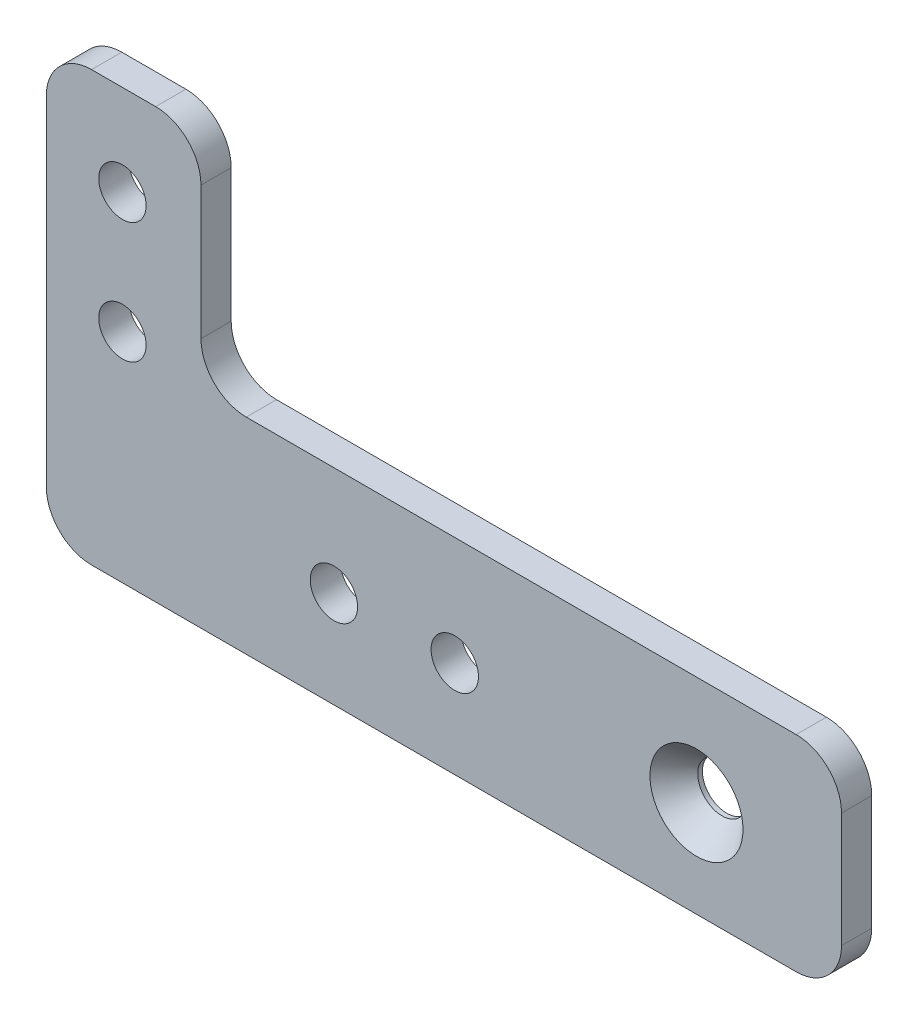
SolidWorks part; units mm, degrees
material "6061-T6 (SS)"
ref_plane "Front Plane" through (0, 0, 0) normal (0, 0, 1) x (1, 0, 0)
ref_plane "Top Plane" through (0, 0, 0) normal (0, 1, 0) x (1, 0, 0)
ref_plane "Right Plane" through (0, 0, 0) normal (1, 0, 0) x (0, 0, -1)
sketch "Sketch1" plane through (0, 0, 0) normal (0, 0, 1) x (1, 0, 0)
  line L0 (-21.59, 23.8125) -> (-37.846, 23.8125) construction
  line L1 (-45.72, -23.8125) -> (45.72, -23.8125)
  line L2 (-45.72, -23.8125) -> (-45.72, 23.8125)
  line L3 (-45.72, 23.8125) -> (45.72, 23.8125)
  line L4 (45.72, -23.8125) -> (45.72, 23.8125)
  line L5 (-45.72, -23.8125) -> (45.72, 23.8125) construction
  line L6 (-45.72, 23.8125) -> (45.72, -23.8125) construction
  line L7 (45.72, 23.8125) -> (-21.59, 23.8125)
  line L8 (45.72, 23.8125) -> (45.72, 0.3175)
  line L9 (45.72, 0.3175) -> (-21.59, 0.3175)
  line L10 (-21.59, 23.8125) -> (-21.59, 0.3175)
  line L11 (-45.72, -23.8125) -> (-37.846, -23.8125)
  line L12 (-45.72, -23.8125) -> (-45.72, 23.8125)
  line L13 (-45.72, 23.8125) -> (-37.846, 23.8125)
  line L14 (-37.846, -23.8125) -> (-37.846, 23.8125)
  line L15 (-37.846, -23.8125) -> (45.72, -23.8125)
  line L16 (-37.846, -23.8125) -> (-37.846, -21.2725)
  line L17 (-37.846, -21.2725) -> (45.72, -21.2725)
  line L18 (45.72, -23.8125) -> (45.72, -21.2725)
  line L19 (-21.59, 23.8125) -> (-37.846, 23.8125) construction
  line L20 (-29.845, 23.8125) -> (-29.845, -21.2725) construction
  circle A0 centre (-29.845, -11.1125) radius 2.4892
  circle A1 centre (-29.845, 1.5875) radius 2.4892
  circle A2 centre (-29.845, 14.2875) radius 2.4892
  circle A4 centre (-7.62, -11.1125) radius 2.4892
  circle A5 centre (5.08, -11.1125) radius 2.4892
  circle A7 centre (30.48, -11.1125) radius 2.4892
  point P0 (0, 0)
  dimension "D7" = 22.225
  dimension "D19" = 4.9784
  dimension "D13" = 25.4
  dimension "D8" = 50.8
  dimension "D1" = 91.44
  dimension "D2" = 9.525
  dimension "D3" = 24.13
  dimension "D4" = 24.13
  dimension "D5" = 7.874
  dimension "D6" = 47.625
  dimension "D9" = 12.7
  dimension "D10" = 12.7
  dimension "D11" = 12.7
  dimension "D12" = 15.875
  dimension "D16" = 2.54
extrude "Boss-Extrude1" add sketch "Sketch1" along normal blind 3.175 contours L14 L17 L4 L9 L10 L3 A5 A4 A2 A1 A0 | A0 region at (-1.4731, -6.6394, 0) region at (-29.845, -11.1125, 0)
fillet "Fillet1" radius 4.7625 6 edges at (-37.846, 23.8125, 1.5875) (-21.59, 23.8125, 1.5875) (-21.59, 0.3175, 1.5875) (45.72, 0.3175, 1.5875) (45.72, -21.2725, 1.5875) (-37.846, -21.2725, 1.5875)
hole_wizard "CSK for #10 Flat Head Machine Screw1" positions "Sketch3" profile "Sketch4" countersink size "#10" standard "ANSI Inch"
sketch "Sketch3" plane through (0, 0, 3.175) normal (0, 0, 1) x (1, 0, 0)
  point P0 (30.48, -11.1125)
sketch "Sketch4" plane through (30.48, -11.1125, 3.175) normal (1, 0, 0) x (0, -1, 0)
  line L0 (0, 0) -> (0, 20.5838)
  line L1 (0, 20.5838) -> (2.5527, 19.05)
  line L2 (2.5527, 19.05) -> (2.5527, 2.6882)
  line L3 (2.5527, 2.6882) -> (4.8895, 0)
  line L5 (4.8895, 0) -> (0, 0)
  line L6 (-2.5527, 2.6882) -> (-4.8895, 0) construction
  line L10 (0, 20.5838) -> (-2.5527, 19.05) construction
  line L11 (0, -6.35) -> (0, 107.95) construction
  dimension "Hole Dia." = 5.1054
  dimension "Hole Depth" = 19.05
  dimension "Near C'Sink Dia." = 9.779
  dimension "Near C'Sink Angle" = 82
  dimension "Drill Angle" = 118
